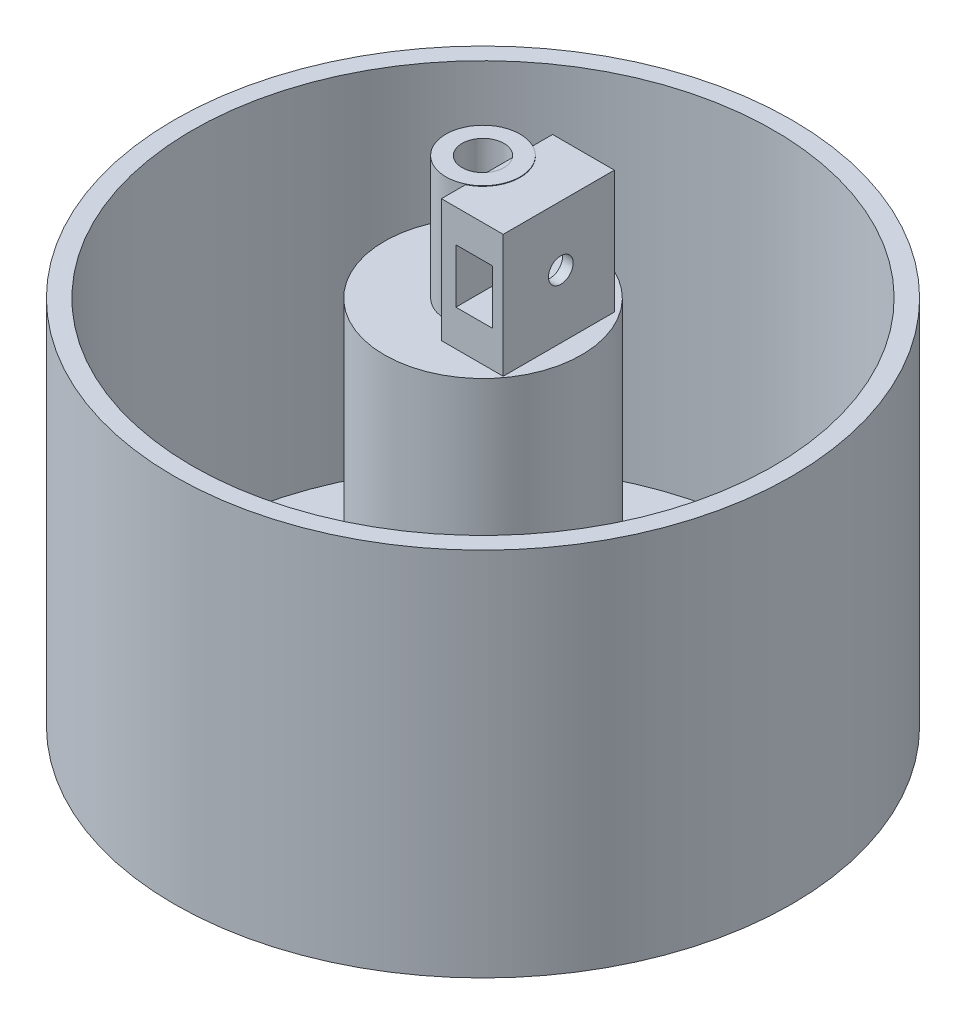
SolidWorks part; units mm, degrees
ref_plane "Front Plane" through (0, 0, 0) normal (0, 0, 1) x (1, 0, 0)
ref_plane "Top Plane" through (0, 0, 0) normal (0, 1, 0) x (1, 0, 0)
ref_plane "Right Plane" through (0, 0, 0) normal (1, 0, 0) x (0, 0, -1)
sketch "Sketch1" plane through (0, 0, 0) normal (0, 1, 0) x (1, 0, 0)
  circle A0 centre (0, 0) radius 6
extrude "Boss-Extrude1" add sketch "Sketch1" along normal blind 20
sketch "Sketch2" plane through (0, 20, 0) normal (0, 1, 0) x (1, 0, 0)
  circle A0 centre (0, 0) radius 3.4
extrude "Cut-Extrude1" cut sketch "Sketch2" against normal blind 13.55 contours A0
ref_plane "Plane1" through (0, 18.26, 0) normal (0, 1, 0) x (1, 0, 0)
ref_axis "Axis1" through (0, 6.45, 0) along (0, 1, 0)
ref_point "Point2"
sketch "Sketch5" plane through (0, 18.26, 0) normal (0, 1, 0) x (1, 0, 0)
  line L0 (0, 0) -> (2.6, 0) construction
  line L2 (2.6, -3.5716) -> (4.1507, -3.5716)
  line L3 (2.6, -3.5716) -> (2.6, 3.6126)
  line L4 (2.6, 3.6126) -> (4.1507, 3.6126)
  line L5 (4.1507, -3.5716) -> (4.1507, 3.6126)
extrude "Boss-Extrude2" add sketch "Sketch5" against normal blind 13.55
sketch "Sketch7" plane through (2.6, 0, 0) normal (-1, 0, 0) x (0, 0, 1)
  line L1 (-8.6717, 19.91) -> (9.3323, 19.91)
  line L2 (-8.6717, 19.91) -> (-8.6717, 0)
  line L3 (-8.6717, 0) -> (9.3323, 0)
  line L4 (9.3323, 19.91) -> (9.3323, 0)
extrude "Boss-Extrude3" add sketch "Sketch7" against normal blind 10
sketch "Sketch6" plane through (2.6, 0, 0) normal (-1, 0, 0) x (0, 0, 1)
  line L1 (-2.1909, 6.45) -> (-2.1909, 19.91) construction
  line L2 (2.1909, 19.91) -> (2.1909, 6.45) construction
  line L3 (-2.1909, 15.4522) -> (2.1909, 15.4522) construction
  circle A0 centre (0, 10.2369) radius 2
extrude "Cut-Extrude2" cut sketch "Sketch6" against normal blind 13.55 and the other way blind 1
ref_axis "Axis2" through (-1.8994, 10.2369, 0) along (-1, 0, 0)
ref_axis "Axis4" through (12.6, 10.2369, 0) along (-1, 0, 0)
ref_plane "Plane3" through (0, 0, 0) normal (0, 0, 1) x (1, 0, 0)
sketch "Sketch9" plane through (0, 0, 0) normal (0, 0, 1) x (1, 0, 0)
  line L0 (10.8765, 10.2369) -> (10.8765, 5.8619)
  line L1 (4.9434, 5.8619) -> (10.8765, 5.8619)
  line L2 (4.9434, 5.8619) -> (4.9434, 10.2369)
  line L3 (4.9434, 10.2369) -> (4.9434, 14.6143)
  line L4 (4.9434, 14.6143) -> (10.8765, 14.6143)
  line L5 (10.8765, 14.6143) -> (10.8765, 10.2369)
  line L6 (12.6, 10.2369) -> (2.6, 10.2369) construction
  point P5 (10.8765, 14.6143)
extrude "Cut-Extrude3" cut sketch "Sketch9" against normal blind 10 and the other way blind 10
sketch "Sketch10" plane through (0, 0, 0) normal (0, -1, 0) x (1, 0, 0)
  circle A0 centre (0, 0) radius 50
extrude "Boss-Extrude4" add sketch "Sketch10" along normal blind 60
sketch "Sketch11" plane through (0, 0, 0) normal (0, 1, 0) x (1, 0, 0)
  line L1 (31.7817, 38.8528) -> (14.4942, 48.0577) construction
  line L2 (14.4942, 48.0577) -> (-5, 49.9462) construction
  line L3 (-5, 49.9462) -> (-23.733, 44.2308) construction
  line L4 (-23.733, 44.2308) -> (-38.8528, 31.7817) construction
  line L5 (-38.8528, 31.7817) -> (-48.0577, 14.4942) construction
  line L6 (-48.0577, 14.4942) -> (-49.9462, -5) construction
  line L7 (-49.9462, -5) -> (-44.2308, -23.733) construction
  line L8 (-44.2308, -23.733) -> (-31.7817, -38.8528) construction
  line L9 (-31.7817, -38.8528) -> (-14.4942, -48.0577) construction
  line L10 (-14.4942, -48.0577) -> (5, -49.9462) construction
  line L11 (5, -49.9462) -> (23.733, -44.2308) construction
  line L12 (23.733, -44.2308) -> (38.8528, -31.7817) construction
  line L13 (38.8528, -31.7817) -> (48.0577, -14.4942) construction
  line L14 (48.0577, -14.4942) -> (49.9462, 5) construction
  line L15 (49.9462, 5) -> (44.2308, 23.733) construction
  line L16 (44.2308, 23.733) -> (31.7817, 38.8528) construction
  circle A0 centre (0, 0) radius 49.2313 construction
  circle A1 centre (5, -49.9462) radius 5
  circle A2 centre (-14.4942, -48.0577) radius 5
  circle A3 centre (-31.7817, -38.8528) radius 5
  circle A4 centre (-44.2308, -23.733) radius 5
  circle A5 centre (-49.9462, -5) radius 5
  circle A6 centre (-48.0577, 14.4942) radius 5
  circle A7 centre (-38.8528, 31.7817) radius 5
  circle A8 centre (-23.733, 44.2308) radius 5
  circle A9 centre (-5, 49.9462) radius 5
  circle A10 centre (14.4942, 48.0577) radius 5
  circle A11 centre (31.7817, 38.8528) radius 5
  circle A12 centre (44.2308, 23.733) radius 5
  circle A13 centre (49.9462, 5) radius 5
  circle A14 centre (48.0577, -14.4942) radius 5
  circle A15 centre (38.8528, -31.7817) radius 5
  circle A16 centre (23.733, -44.2308) radius 5
sketch "Sketch12" plane through (0, 0, 0) normal (0, 1, 0) x (1, 0, 0)
  circle A0 centre (0, 0) radius 47.0828
  circle A1 centre (0, 0) radius 15.9579
extrude "Cut-Extrude5" cut sketch "Sketch12" against normal blind 57
